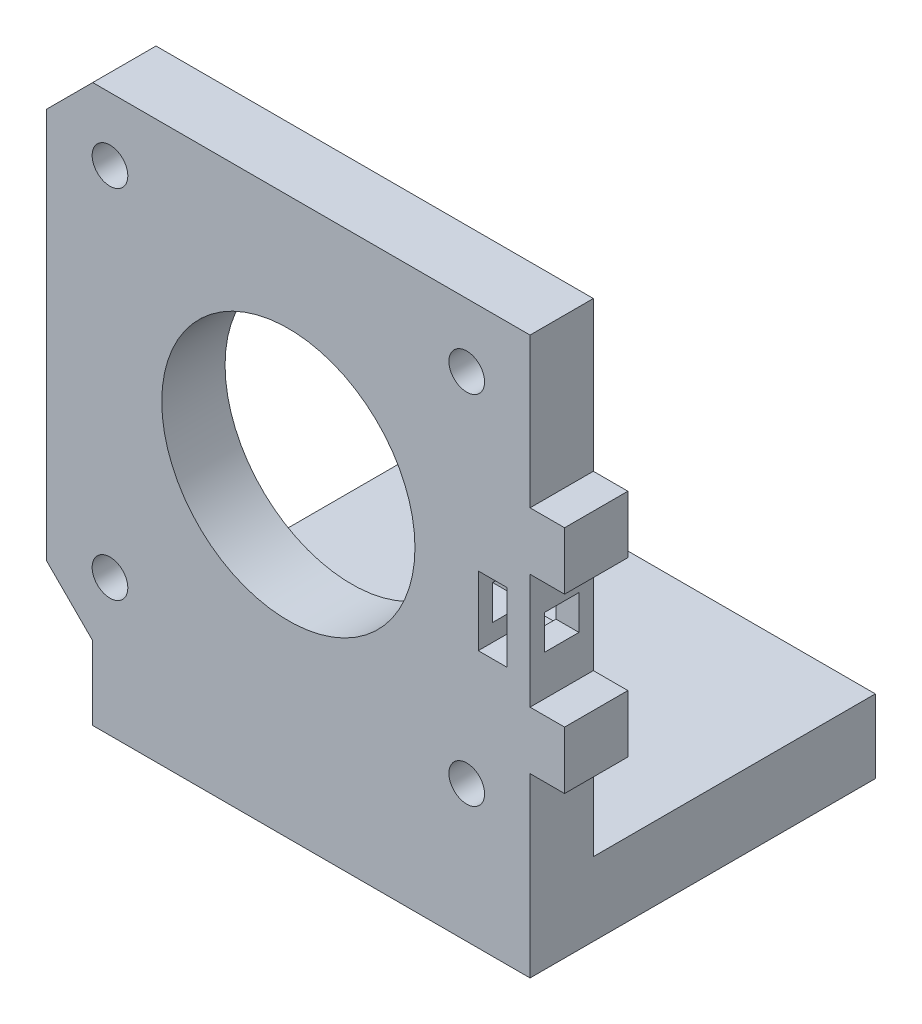
SolidWorks part; units mm, degrees
ref_plane "Alzado" through (0, 0, 0) normal (0, 0, 1) x (1, 0, 0)
ref_plane "Planta" through (0, 0, 0) normal (0, 1, 0) x (1, 0, 0)
ref_plane "Vista lateral" through (0, 0, 0) normal (1, 0, 0) x (0, 0, -1)
sketch "Croquis1" plane through (0, 0, 0) normal (0, 0, 1) x (1, 0, 0)
  line L0 (0, 4) -> (0, 38)
  line L1 (4, 42) -> (42, 42)
  line L2 (42, 42) -> (42, 0)
  line L3 (42, 0) -> (4, 0)
  line L4 (0, 0) -> (0.3166, 0.4221)
  line L5 (0, 38) -> (4, 42)
  line L6 (4, 0) -> (0, 4)
  circle A0 centre (5.5, 36.5) radius 1.55
  circle A1 centre (5.5, 5.5) radius 1.55
  circle A2 centre (36.5, 5.5) radius 1.55
  circle A3 centre (36.5, 36.5) radius 1.55
  circle A4 centre (21, 21) radius 11
  point P1 (0, 42)
  dimension "D3" = 3.1
  dimension "D4" = 3.1
  dimension "D5" = 3.1
  dimension "D6" = 3.1
  dimension "D13" = 22
  dimension "D1" = 42
  dimension "D2" = 42
  dimension "D7" = 31
  dimension "D10" = 31
  dimension "D11" = 5.5
  dimension "D12" = 5.5
  dimension "D14" = 21
  dimension "D15" = 21
extrude "Saliente-Extruir1" add sketch "Croquis1" along normal blind 5.5 contours L6 L3 L2 L1 L5 L0 A4 A3 A2 A1 A0 region at (0.594, 21, 0)
sketch "Croquis2" plane through (0, 0, 5.5) normal (0, 0, 1) x (1, 0, 0)
  line L0 (42, 0) -> (4, 0) construction
  line L1 (42, 0) -> (4, 0)
  line L2 (4, 0) -> (4, -6.38)
  line L3 (4, -6.38) -> (42, -6.38)
  line L4 (42, -6.38) -> (42, 0)
  dimension "D1" = 6.38
extrude "Saliente-Extruir2" add sketch "Croquis2" against normal blind 30
sketch "Croquis3" plane through (42, 0, 0) normal (1, 0, 0) x (0, 0, -1)
  line L0 (-5.5, 29) -> (0, 29)
  line L1 (-5.5, 42) -> (-5.5, -6.38) construction
  line L2 (0, 42) -> (0, 0) construction
  line L3 (0, 29) -> (0, 24)
  line L4 (0, 24) -> (-5.5, 24)
  line L5 (-5.5, 24) -> (-5.5, 29)
  line L6 (-5.5, 42) -> (0, 42) construction
  line L7 (-5.5, 14) -> (0, 14)
  line L8 (0, 14) -> (0, 9)
  line L9 (0, 9) -> (-5.5, 9)
  line L10 (-5.5, 9) -> (-5.5, 14)
  dimension "D1" = 5
  dimension "D2" = 13
  dimension "D3" = 5
  dimension "D4" = 10
extrude "Saliente-Extruir3" add sketch "Croquis3" along normal blind 3
sketch "Croquis6" plane through (42, 0, 0) normal (1, 0, 0) x (0, 0, -1)
  line L0 (-5.5, 24) -> (0, 24) construction
  line L1 (-4.25, 20.5) -> (-1.25, 20.5)
  line L2 (-4.25, 20.5) -> (-4.25, 17.5)
  line L3 (-4.25, 17.5) -> (-1.25, 17.5)
  line L4 (-1.25, 20.5) -> (-1.25, 17.5)
  line L5 (-4.25, 20.5) -> (-1.25, 17.5) construction
  line L6 (-4.25, 17.5) -> (-1.25, 20.5) construction
  line L8 (-5.5, 24) -> (-5.5, 14) construction
  point P0 (-2.75, 19)
  dimension "D1" = 3
  dimension "D2" = 3
  dimension "D3" = 5
  dimension "D4" = 2.75
extrude "Cortar-Extruir2" cut sketch "Croquis6" against normal blind 8
sketch "Croquis7" plane through (0, 0, 5.5) normal (0, 0, 1) x (1, 0, 0)
  line L0 (37.5, 22) -> (40, 22)
  line L1 (40, 22) -> (40, 16)
  line L2 (40, 16) -> (37.5, 16)
  line L3 (37.5, 16) -> (37.5, 22)
  line L4 (42, 24) -> (42, 14) construction
  line L5 (42, 24) -> (42, 14)
  point P6 (42, 19)
  point P7 (40, 19)
  dimension "D1" = 2.5
  dimension "D2" = 6
  dimension "D3" = 2
extrude "Cortar-Extruir3" cut sketch "Croquis7" against normal through all contours L3 L2 L1 L0 region at (38.75, 19, 5.5)
